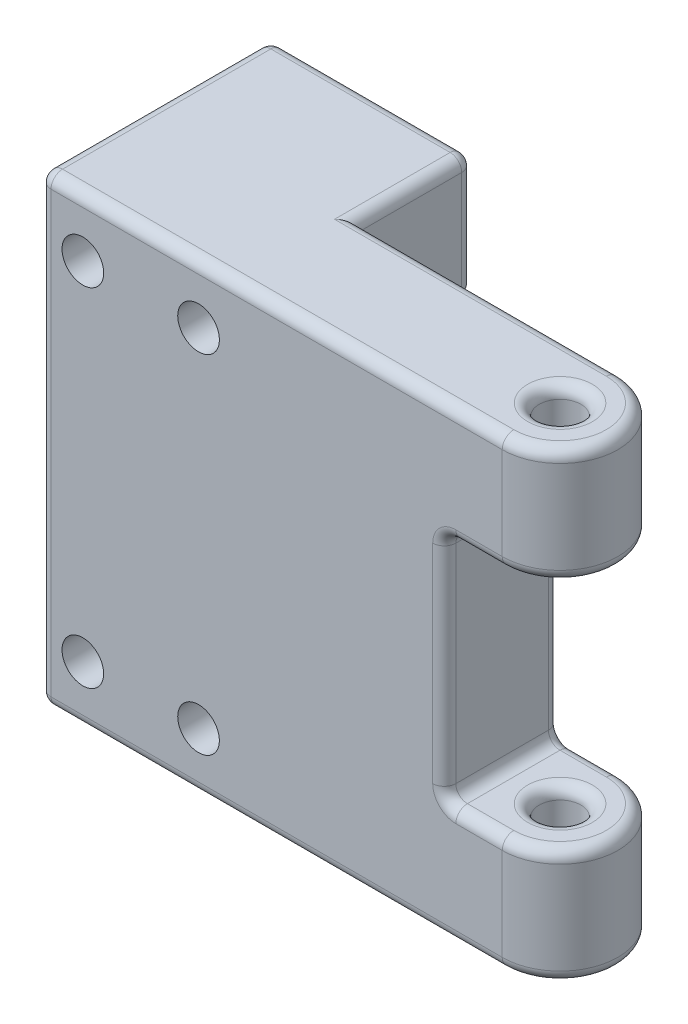
SolidWorks part; units mm, degrees
ref_plane "Front Plane" through (0, 0, 0) normal (0, 0, 1) x (1, 0, 0)
ref_plane "Top Plane" through (0, 0, 0) normal (0, 1, 0) x (1, 0, 0)
ref_plane "Right Plane" through (0, 0, 0) normal (1, 0, 0) x (0, 0, -1)
sketch "Sketch1" plane through (0, 0, 0) normal (0, 1, 0) x (1, 0, 0)
  line L1 (0, 0) -> (26.035, 0)
  line L5 (0, 0) -> (-2.54, 0)
  line L7 (26.035, -12.7) -> (-24.765, -12.7)
  line L8 (-24.765, 12.7) -> (-24.765, -12.7)
  line L11 (-24.765, 12.7) -> (-2.54, 12.7)
  line L12 (-2.54, 0) -> (-2.54, 12.7)
  arc A0 (26.035, -12.7) -> (26.035, 0) centre (26.035, -6.35) ccw
  circle A1 centre (26.035, -6.35) radius 2.286
  dimension "D1" = 22.225
  dimension "D4" = 6.35
  dimension "D6" = 4.572
  dimension "D2" = 12.7
  dimension "D3" = 50.8
  dimension "D5" = 2.54
  dimension "D7" = 12.7
extrude "Boss-Extrude1" add sketch "Sketch1" along normal blind 50.8
sketch "Sketch2" plane through (0, 0, 12.7) normal (0, 0, 1) x (1, 0, 0)
  line L0 (-24.765, 0) -> (26.035, 0) construction
  line L1 (-24.765, 0) -> (-2.54, 0) construction
  line L2 (32.385, 0) -> (32.385, 50.8) construction
  line L3 (32.385, 38.1) -> (19.6731, 38.1)
  line L4 (32.385, 38.1) -> (32.385, 12.7)
  line L5 (32.385, 12.7) -> (19.6731, 12.7)
  line L6 (19.6731, 38.1) -> (19.6731, 12.7)
  line L7 (32.385, 50.8) -> (26.035, 50.8) construction
  line L9 (-2.54, 50.8) -> (-2.54, 0) construction
  circle A0 centre (-20.0025, 6.35) radius 2.286
  circle A1 centre (-7.3025, 6.35) radius 2.286
  circle A2 centre (-7.3025, 44.45) radius 2.286
  circle A3 centre (-20.0025, 44.45) radius 2.286
  point P21 (0, 0)
  point P22 (-6.4457, 0)
  point P23 (0, 0)
  point P26 (-13.6525, 0)
  dimension "D1" = 6.35
  dimension "D2" = 6.35
  dimension "D3" = 4.572
  dimension "D6" = 12.7
  dimension "D7" = 12.7119
  dimension "D8" = 12.7
  dimension "D4" = 2
  dimension "D5" = 2
extrude "Cut-Extrude1" cut sketch "Sketch2" against normal through all and the other way through all
sketch "Sketch3" plane through (-2.54, 0, 0) normal (1, 0, 0) x (0, 0, -1)
  line L0 (0, 50.8) -> (0, 0) construction
  line L1 (0, 12.7) -> (12.7, 12.7)
  line L2 (0, 12.7) -> (0, 38.1)
  line L3 (0, 38.1) -> (12.7, 38.1)
  line L4 (12.7, 12.7) -> (12.7, 38.1)
  line L5 (12.7, 50.8) -> (12.7, 0) construction
  line L6 (0, 0) -> (12.7, 0) construction
  dimension "D1" = 12.7
  dimension "D2" = 25.4
extrude "Cut-Extrude2" cut sketch "Sketch3" against normal through all
fillet "Fillet1" radius 1.27 39 edges at (-24.765, 25.4, 12.7) (22.8541, 38.1, 12.7) (19.6731, 25.4, 12.7) (22.8541, 12.7, 12.7) (32.385, 50.8, 6.35) (0.635, 50.8, 12.7) (-24.765, 50.8, 0) (-2.54, 50.8, -6.35) (26.035, 50.8, 8.636) (-13.6525, 0, -12.7) (-24.765, 0, 0) (0.635, 0, 12.7) (32.385, 0, 6.35) (-2.54, 0, -6.35) (26.035, 0, 8.636) (-13.6525, 12.7, -12.7) (22.8541, 38.1, 0) (11.7475, 50.8, 0) (-13.6525, 38.1, 0) (-13.6525, 12.7, 0) (11.7475, 0, 0) (22.8541, 12.7, 0) (19.6731, 25.4, 0) (-5.0165, 44.45, -12.7) (-17.7165, 44.45, -12.7) (-13.6525, 50.8, -12.7) (-24.765, 44.45, -12.7) (-13.6525, 38.1, -12.7) (-2.54, 44.45, -12.7) (-2.54, 6.35, -12.7) (-24.765, 6.35, -12.7) (32.385, 12.7, 6.35) (28.321, 12.7, 6.35) (32.385, 38.1, 6.35) (26.035, 38.1, 8.636) (-17.7165, 6.35, -12.7) (19.6731, 12.7, 6.35) (19.6731, 38.1, 6.35) (-5.0165, 6.35, -12.7)
